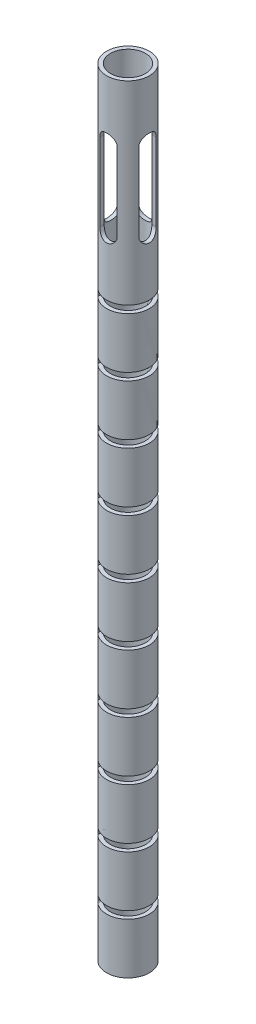
SolidWorks part; units mm, degrees
material "Nickel"
ref_plane "Front Plane" through (0, 0, 0) normal (0, 0, 1) x (1, 0, 0)
ref_plane "Top Plane" through (0, 0, 0) normal (0, 1, 0) x (1, 0, 0)
ref_plane "Right Plane" through (0, 0, 0) normal (1, 0, 0) x (0, 0, -1)
sketch "Sketch2" plane through (0, 0, 0) normal (0, 1, 0) x (1, 0, 0)
  circle A0 centre (0, 0) radius 0.45
  circle A1 centre (0, 0) radius 0.55
  dimension "D1" = 1.1
  dimension "D2" = 0.9
extrude "Boss-Extrude1" add sketch "Sketch2" along normal blind 20
sketch "Sketch3" plane through (0, 0, 0) normal (0, 1, 0) x (1, 0, 0)
  line L0 (-0.385, -0.4602) -> (-0.385, 0.4602)
  arc A0 (-0.385, -0.4602) -> (-0.385, 0.4602) centre (0, 0) ccw
  dimension "D2" = 0.6
  dimension "D1" = 0.385
extrude "Cut-Extrude1" cut sketch "Sketch3" against normal blind 0.1901 from offset 1.5
ref_axis "Axis1" through (0, 31.5, 0) along (0, -1, 0)
pattern_linear "LPattern2" count 10 spacing 1.5 along (0, 1, 0) of "Cut-Extrude1"
sketch "Sketch5" plane through (0, 0, 0) normal (0, 0, 1) x (1, 0, 0)
  line L0 (0, 18.5) -> (0, 16.5) construction
  line L1 (0.225, 18.5) -> (0.225, 16.5)
  line L2 (-0.225, 18.5) -> (-0.225, 16.5)
  line L3 (0.45, 20) -> (-0.45, 20) construction
  arc A0 (0.225, 18.5) -> (-0.225, 18.5) centre (0, 18.5) ccw
  arc A1 (-0.225, 16.5) -> (0.225, 16.5) centre (0, 16.5) ccw
  point P2 (0, 17.5)
  dimension "D2" = 0.45
  dimension "D1" = 2
  dimension "D3" = 2.5
extrude "Cut-Extrude3" cut sketch "Sketch5" against normal through all
pattern_circular "CirPattern2" count 4 over 360 about axis through (0, 31.5, 0) along (0, -1, 0) of "Cut-Extrude3"
fillet "Fillet2" radius 0.02 2 edges at (-0.385, 1.5, 0.3129) (-0.385, 1.3099, 0.3129)
ref_plane "Plane1" through (0.55, 0, 0) normal (1, 0, 0) x (0, 0, -1)
sketch "Sketch6" plane through (0.55, 0, 0) normal (1, 0, 0) x (0, 0, -1)
  line L0 (0, 0) -> (0, 20) construction
  line L1 (0.55, 20) -> (-0.55, 20) construction
  point P3 (0, 19.0718)
  point P4 (0, 20)
equation "\"l\"= 15mm"
equation "\"u\"= 1.3099"
equation "\"h\"= 0.1901mm"
equation "\"D1@Boss-Extrude1\"=\"l\"+5mm"
equation "\"D19@Cut-Extrude1\"=\"u\"+\"h\""
equation "\"D1@Cut-Extrude1\"=\"h\""
equation "\"D3@LPattern2\"=\"u\"+\"h\""
